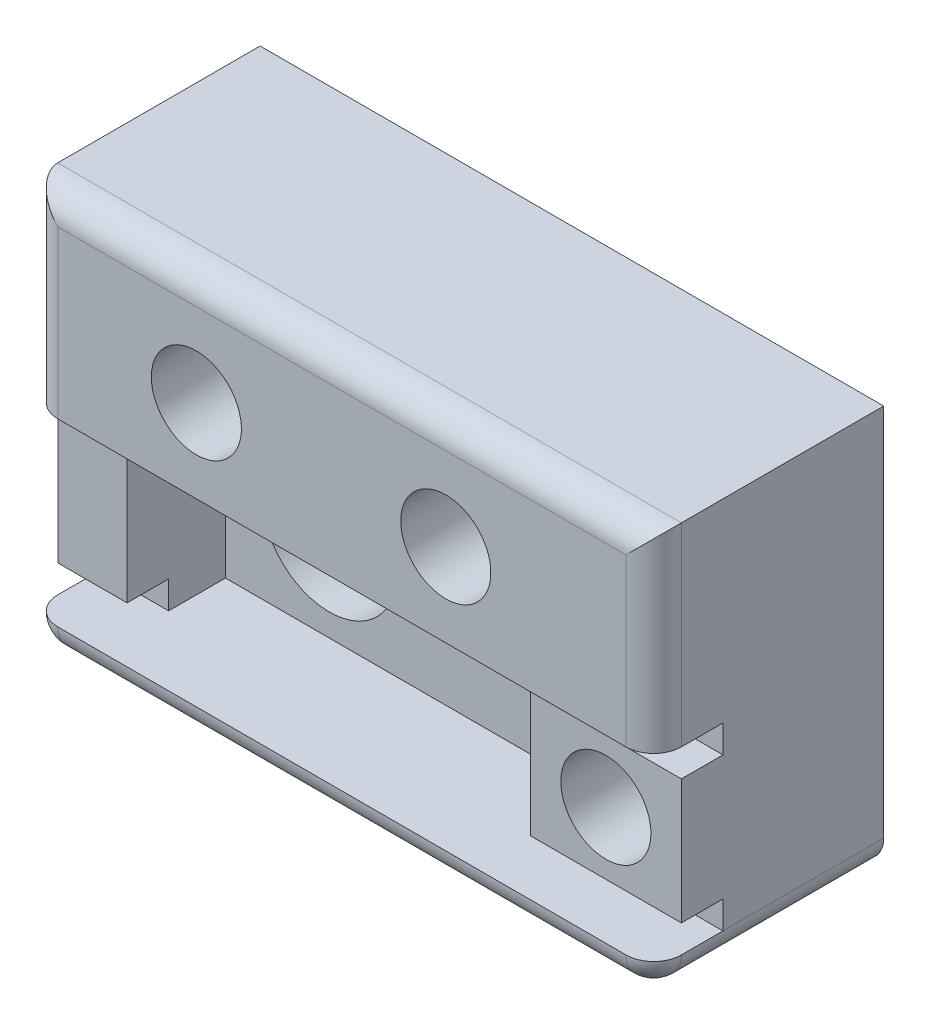
SolidWorks part; units mm, degrees
ref_plane "Front Plane" through (0, 0, 0) normal (0, 0, 1) x (1, 0, 0)
ref_plane "Top Plane" through (0, 0, 0) normal (0, 1, 0) x (1, 0, 0)
ref_plane "Right Plane" through (0, 0, 0) normal (1, 0, 0) x (0, 0, -1)
sketch "Sketch1" plane through (0, 0, 0) normal (0, 0, 1) x (1, 0, 0)
  line L0 (45, 12) -> (12.5, 12) construction
  line L3 (0, 32.5) -> (45, 32.5)
  line L5 (45, -17.5) -> (0, -17.5)
  line L6 (45, 32.5) -> (45, -17.5)
  line L14 (12.5, 12) -> (12.5, -3) construction
  line L15 (12.5, -3) -> (32.5, -3) construction
  line L16 (0, 32.5) -> (0, -17.5)
  circle A0 centre (12.5, 12) radius 4.875
  circle A1 centre (32.5, -3) radius 4.875
  dimension "D4" = 9.75
  dimension "D7" = 15
  dimension "D5" = 20.5
  dimension "D1" = 12
  dimension "D2" = 12.5
  dimension "D3" = 50
  dimension "D6" = 12.5
  dimension "D8" = 12.5
  dimension "D9" = 20
extrude "Boss-Extrude1" add sketch "Sketch1" along normal blind 7.5
sketch "Sketch4" plane through (0, 0, 0) normal (0, 0, -1) x (-1, 0, 0)
  line L0 (-5, 5.5) -> (-34.1, 5.5)
  line L1 (-34.1, 18.5) -> (-5, 18.5)
  line L3 (-34.1, 5.5) -> (-34.1, 18.5)
  line L4 (-45, 32.5) -> (-45, -17.5)
  line L5 (-45, -17.5) -> (0, -17.5)
  line L7 (0, 32.5) -> (-45, 32.5)
  line L11 (0, 32.5) -> (-45, 32.5)
  line L14 (-5, 18.5) -> (-5, 5.5)
  line L16 (-45, -17.5) -> (-45, 32.5) construction
  line L17 (0, 32.5) -> (0, -17.5) construction
  line L18 (-45, 3.5) -> (0, 3.5)
  line L22 (-45, 32.5) -> (-45, 3.5)
  line L23 (0, -17.5) -> (0, 32.5)
  line L24 (0, 3.5) -> (0, 32.5)
  dimension "D2" = 27
  dimension "D3" = 14
  dimension "D4" = 29.1
  dimension "D5" = 5
  dimension "D6" = 2
  dimension "D1" = 0
extrude "Boss-Extrude4" add sketch "Sketch4" along normal blind 7.1
sketch "Sketch18" plane through (0, 0, -7.1) normal (0, 0, -1) x (-1, 0, 0)
  line L7 (-45, 32.5) -> (-45, 3.5) construction
  line L9 (-45, 32.5) -> (0, 32.5)
  line L10 (-45, 32.5) -> (-45, 18.5)
  line L11 (-45, 18.5) -> (0, 18.5)
  line L19 (0, 3.5) -> (0, 32.5) construction
  line L21 (-45, 3.5) -> (0, 3.5) construction
  line L22 (-45, 5.5) -> (0, 5.5)
  line L23 (0, 32.5) -> (0, 18.5)
  line L24 (-45, 5.5) -> (-45, 3.5)
  line L25 (-45, 3.5) -> (0, 3.5)
  line L26 (0, 5.5) -> (0, 3.5)
  dimension "D3" = 27
  dimension "D1" = 14
extrude "Boss-Extrude7" add sketch "Sketch18" along normal blind 2
sketch "Sketch19" plane through (0, 0, 7.5) normal (0, 0, 1) x (1, 0, 0)
  line L0 (12.5, 12) -> (12.5, 32.5) construction
  line L1 (0, -17.5) -> (20, -17.5)
  line L2 (0, -17.5) -> (0, -0.5)
  line L3 (0, -0.5) -> (20, -0.5)
  line L4 (20, -17.5) -> (20, -0.5)
  line L5 (45, 32.5) -> (0, 32.5) construction
  line L6 (32.5, -3) -> (32.5, -17.5) construction
  line L7 (0, -17.5) -> (45, -17.5) construction
  line L8 (12.5, 12) -> (0, 12) construction
  line L9 (0, 32.5) -> (0, -17.5) construction
  dimension "D1" = 12.5
  dimension "D2" = 12.5
extrude "Cut-Extrude1" cut sketch "Sketch19" against normal up to next
sketch "Sketch21" plane through (0, -17.5, 0) normal (0, -1, 0) x (1, 0, 0)
  line L1 (45, 7.5) -> (0, 7.5)
  line L2 (45, 7.5) -> (45, -9.1)
  line L3 (45, -9.1) -> (0, -9.1)
  line L4 (0, 7.5) -> (0, -9.1)
extrude "Cut-Extrude3" cut sketch "Sketch21" against normal blind 21
sketch "Sketch25" plane through (0, 0, -7.1) normal (0, 0, -1) x (-1, 0, 0)
  line L0 (-34.1, 12) -> (-45, 12) construction
  line L1 (-34.1, 18.5) -> (-34.1, 5.5) construction
  line L2 (-45, 18.5) -> (-45, 5.5) construction
  circle A0 centre (-39.55, 12) radius 1.65
  dimension "D1" = 3.3
extrude "Cut-Extrude7" cut sketch "Sketch25" against normal through all
sketch "Sketch26" plane through (0, 0, -7.1) normal (0, 0, -1) x (-1, 0, 0)
  circle A0 centre (-39.55, 12) radius 3.25
  dimension "D1" = 6.5
extrude "Cut-Extrude8" cut sketch "Sketch26" against normal blind 12.6
fillet "Fillet1" radius 2 8 edges at (45, 4.5, -9.1) (45, 25.5, -9.1) (0, 25.5, -9.1) (0, 4.5, -9.1) (45, 3.5, -0.8) (22.5, 32.5, -9.1) (0, 3.5, -0.8) (22.5, 3.5, -9.1)
sketch "Sketch27" plane through (0, 0, -9.1) normal (0, 0, -1) x (-1, 0, 0)
  line L0 (-2, 24.5) -> (-43, 24.5) construction
  line L1 (-2, 18.5) -> (-2, 30.5) construction
  line L2 (-43, 30.5) -> (-43, 18.5) construction
  line L3 (0, 32.5) -> (0, 18.5) construction
  line L4 (-45, 18.5) -> (-45, 32.5) construction
  circle A0 centre (-12, 24.5) radius 1.65
  circle A1 centre (-30, 24.5) radius 1.65
  dimension "D1" = 3.3
  dimension "D2" = 12
  dimension "D3" = 15
extrude "Cut-Extrude9" cut sketch "Sketch27" against normal through all
sketch "Sketch29" plane through (0, 0, -7.1) normal (0, 0, -1) x (-1, 0, 0)
  line L0 (0, 12) -> (-45, 12) construction
  line L1 (0, 5.5) -> (-60, 5.5)
  line L2 (0, 5.5) -> (0, 7.5)
  line L3 (0, 7.5) -> (-60, 7.5)
  line L4 (-60, 5.5) -> (-60, 7.5)
  line L5 (0, 5.5) -> (0, 18.5) construction
  line L6 (-45, 18.5) -> (-45, 5.5) construction
  line L7 (0, 16.5) -> (-60, 16.5)
  line L8 (-60, 18.5) -> (-60, 16.5)
  line L9 (0, 18.5) -> (-60, 18.5)
  line L10 (0, 18.5) -> (0, 16.5)
  dimension "D1" = 2
  dimension "D2" = 60
extrude "Cut-Extrude11" cut sketch "Sketch29" against normal blind 3
sketch "Sketch30" plane through (0, 0, -9.1) normal (0, 0, -1) x (-1, 0, 0)
  circle A0 centre (-30, 24.5) radius 3.25
  circle A1 centre (-12, 24.5) radius 3.25
  dimension "D1" = 6.5
extrude "Cut-Extrude12" cut sketch "Sketch30" against normal blind 14.6
mirror "Mirror1" about plane through (0, 0, 7.5) normal (0, 0, -1) of bodies 203 199
sketch "Sketch28" plane through (0, 3.5, 0) normal (0, -1, 0) x (1, 0, 0)
  line L1 (0, 7.5) -> (60, 7.5)
  line L2 (0, 7.5) -> (0, -23.6809)
  line L3 (0, -23.6809) -> (60, -23.6809)
  line L4 (60, 7.5) -> (60, -23.6809)
  line L5 (0, -4.1) -> (0, 19.1) construction
  point P8 (0, 7.5)
  dimension "D1" = 60
extrude "Cut-Extrude10" cut sketch "Sketch28" against normal through all
